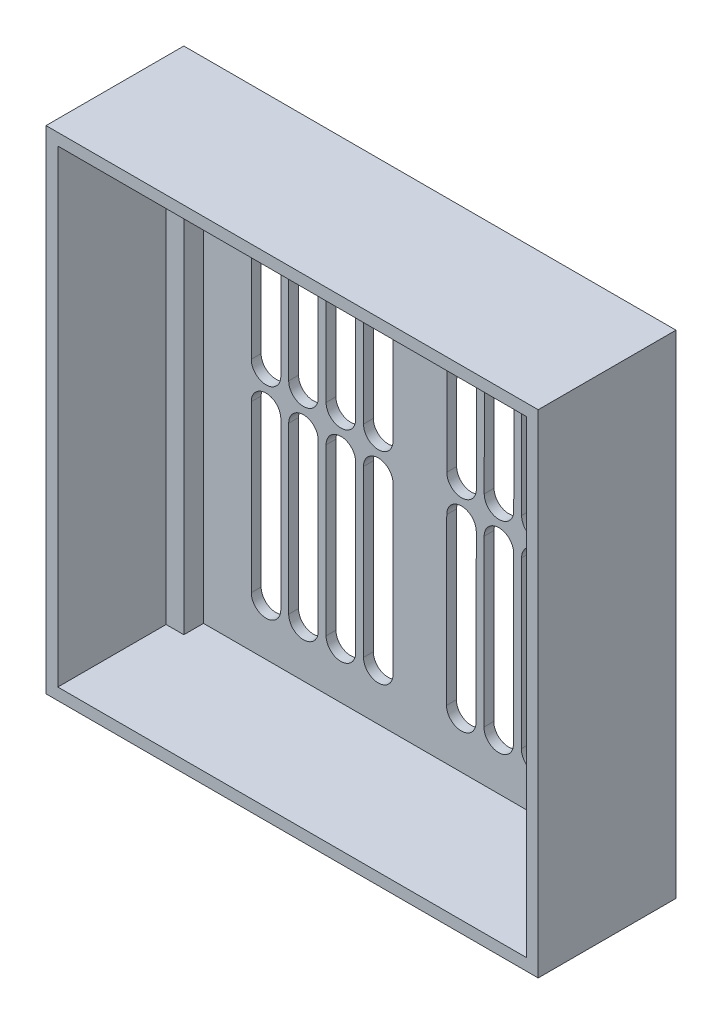
SolidWorks part; units mm, degrees
ref_plane "Plano frontal" through (0, 0, 0) normal (0, 0, 1) x (1, 0, 0)
ref_plane "Plano superior" through (0, 0, 0) normal (0, 1, 0) x (1, 0, 0)
ref_plane "Plano direito" through (0, 0, 0) normal (1, 0, 0) x (0, 0, -1)
sketch "Esboço1" plane through (0, 0, 0) normal (0, 0, 1) x (1, 0, 0)
  line L1 (-16.5696, 239.8339) -> (233.4304, 239.8339)
  line L2 (-16.5696, 239.8339) -> (-16.5696, -10.1661)
  line L3 (-16.5696, -10.1661) -> (233.4304, -10.1661)
  line L4 (233.4304, 239.8339) -> (233.4304, -10.1661)
  dimension "D1" = 250
  dimension "D2" = 250
extrude "Ressalto-extrusão1" add sketch "Esboço1" along normal blind 70 contours L2 L1 L4 L3
sketch "Esboço2" plane through (0, 0, 70) normal (0, 0, 1) x (1, 0, 0)
  line L0 (233.4304, 239.8339) -> (233.4304, -10.1661) construction
  line L1 (-10.5696, 233.8339) -> (227.4304, 233.8339)
  line L2 (-10.5696, 233.8339) -> (-10.5696, -4.1661)
  line L3 (-10.5696, -4.1661) -> (227.4304, -4.1661)
  line L4 (227.4304, 233.8339) -> (227.4304, -4.1661)
  line L5 (-16.5696, 239.8339) -> (233.4304, 239.8339) construction
  line L6 (-16.5696, 239.8339) -> (-16.5696, -10.1661) construction
  line L7 (-16.5696, -10.1661) -> (233.4304, -10.1661) construction
  dimension "D1" = 6
  dimension "D2" = 6
  dimension "D3" = 6
  dimension "D4" = 6
extrude "Corte-extrusão1" cut sketch "Esboço2" against normal blind 55
sketch "Esboço3" plane through (0, 0, 15) normal (0, 0, 1) x (1, 0, 0)
  line L0 (16.5131, 123.2364) -> (114.7807, 123.244)
  line L1 (16.3207, 123.1057) -> (16.3131, 223.614)
  line L2 (16.3748, 223.7141) -> (114.8731, 223.7141)
  line L3 (114.7807, 123.244) -> (114.7731, 223.5216)
  line L4 (215.3156, 223.7537) -> (117.0479, 223.7536)
  line L5 (215.5079, 223.8844) -> (215.5079, 123.3761)
  line L6 (117.0479, 123.4759) -> (215.5079, 123.3761)
  line L7 (117.0479, 223.7536) -> (117.0479, 123.4759)
  line L10 (16.567, 20.9373) -> (114.8346, 20.9449)
  line L11 (16.3746, 20.8067) -> (16.367, 121.3149)
  line L12 (16.4288, 121.4073) -> (99.2081, 121.4137)
  line L13 (114.8346, 20.9449) -> (114.827, 121.2225)
  line L14 (215.3478, 121.4314) -> (117.0801, 121.4238)
  line L15 (215.5401, 121.5621) -> (215.5477, 21.0538)
  line L16 (215.486, 20.9614) -> (116.9877, 20.9538)
  line L17 (117.0801, 121.4238) -> (117.0877, 21.1462)
  line L21 (-16.5696, -10.1661) -> (233.4304, -10.1661) construction
  line L23 (114.7807, 123.244) -> (117.0801, 121.4238) construction
  line L24 (99.2081, 121.4137) -> (114.827, 121.2225)
  line L25 (-16.5696, 239.8339) -> (233.4304, -10.1661) construction
  line L26 (-16.5696, -10.1661) -> (233.4304, 239.8339) construction
  arc A0 (59.4431, 138.154) -> (59.4431, 125.154) centre (59.4431, 131.654) ccw
  arc A1 (59.4431, 125.154) -> (59.4431, 138.154) centre (59.4431, 131.654) ccw
  arc A2 (40.4431, 138.154) -> (40.4431, 125.154) centre (40.4431, 131.654) ccw
  arc A3 (40.4431, 125.154) -> (40.4431, 138.154) centre (40.4431, 131.654) ccw
  arc A4 (40.4431, 152.154) -> (40.4431, 139.154) centre (40.4431, 145.654) ccw
  arc A5 (40.4431, 139.154) -> (40.4431, 152.154) centre (40.4431, 145.654) ccw
  arc A6 (59.4431, 152.154) -> (59.4431, 139.154) centre (59.4431, 145.654) ccw
  arc A7 (59.4431, 139.154) -> (59.4431, 152.154) centre (59.4431, 145.654) ccw
  arc A8 (78.4431, 152.154) -> (78.4431, 139.154) centre (78.4431, 145.654) ccw
  arc A9 (78.4431, 139.154) -> (78.4431, 152.154) centre (78.4431, 145.654) ccw
  arc A10 (78.4431, 138.154) -> (78.4431, 125.154) centre (78.4431, 131.654) ccw
  arc A11 (78.4431, 125.154) -> (78.4431, 138.154) centre (78.4431, 131.654) ccw
  arc A12 (97.4431, 138.154) -> (97.4431, 125.154) centre (97.4431, 131.654) ccw
  arc A13 (97.4431, 125.154) -> (97.4431, 138.154) centre (97.4431, 131.654) ccw
  arc A14 (97.4431, 152.154) -> (97.4431, 139.154) centre (97.4431, 145.654) ccw
  arc A15 (97.4431, 139.154) -> (97.4431, 152.154) centre (97.4431, 145.654) ccw
  arc A16 (97.4431, 166.154) -> (97.4431, 153.154) centre (97.4431, 159.654) ccw
  arc A17 (97.4431, 153.154) -> (97.4431, 166.154) centre (97.4431, 159.654) ccw
  arc A18 (78.4431, 166.154) -> (78.4431, 153.154) centre (78.4431, 159.654) ccw
  arc A19 (78.4431, 153.154) -> (78.4431, 166.154) centre (78.4431, 159.654) ccw
  arc A20 (59.4431, 166.154) -> (59.4431, 153.154) centre (59.4431, 159.654) ccw
  arc A21 (59.4431, 153.154) -> (59.4431, 166.154) centre (59.4431, 159.654) ccw
  arc A22 (40.4431, 166.154) -> (40.4431, 153.154) centre (40.4431, 159.654) ccw
  arc A23 (40.4431, 153.154) -> (40.4431, 166.154) centre (40.4431, 159.654) ccw
  arc A24 (40.4431, 180.154) -> (40.4431, 167.154) centre (40.4431, 173.654) ccw
  arc A25 (40.4431, 167.154) -> (40.4431, 180.154) centre (40.4431, 173.654) ccw
  arc A26 (59.4431, 180.154) -> (59.4431, 167.154) centre (59.4431, 173.654) ccw
  arc A27 (59.4431, 167.154) -> (59.4431, 180.154) centre (59.4431, 173.654) ccw
  arc A28 (78.4431, 180.154) -> (78.4431, 167.154) centre (78.4431, 173.654) ccw
  arc A29 (78.4431, 167.154) -> (78.4431, 180.154) centre (78.4431, 173.654) ccw
  arc A30 (97.4431, 180.154) -> (97.4431, 167.154) centre (97.4431, 173.654) ccw
  arc A31 (97.4431, 167.154) -> (97.4431, 180.154) centre (97.4431, 173.654) ccw
  arc A32 (97.4431, 194.154) -> (97.4431, 181.154) centre (97.4431, 187.654) ccw
  arc A33 (97.4431, 181.154) -> (97.4431, 194.154) centre (97.4431, 187.654) ccw
  arc A34 (78.4431, 194.154) -> (78.4431, 181.154) centre (78.4431, 187.654) ccw
  arc A35 (78.4431, 181.154) -> (78.4431, 194.154) centre (78.4431, 187.654) ccw
  arc A36 (59.4431, 194.154) -> (59.4431, 181.154) centre (59.4431, 187.654) ccw
  arc A37 (59.4431, 181.154) -> (59.4431, 194.154) centre (59.4431, 187.654) ccw
  arc A38 (40.4431, 194.154) -> (40.4431, 181.154) centre (40.4431, 187.654) ccw
  arc A39 (40.4431, 181.154) -> (40.4431, 194.154) centre (40.4431, 187.654) ccw
  arc A40 (40.4431, 208.154) -> (40.4431, 195.154) centre (40.4431, 201.654) ccw
  arc A41 (40.4431, 195.154) -> (40.4431, 208.154) centre (40.4431, 201.654) ccw
  arc A42 (59.4431, 208.154) -> (59.4431, 195.154) centre (59.4431, 201.654) ccw
  arc A43 (59.4431, 195.154) -> (59.4431, 208.154) centre (59.4431, 201.654) ccw
  arc A44 (78.4431, 208.154) -> (78.4431, 195.154) centre (78.4431, 201.654) ccw
  arc A45 (78.4431, 195.154) -> (78.4431, 208.154) centre (78.4431, 201.654) ccw
  arc A46 (97.4431, 208.154) -> (97.4431, 195.154) centre (97.4431, 201.654) ccw
  arc A47 (97.4431, 195.154) -> (97.4431, 208.154) centre (97.4431, 201.654) ccw
  arc A48 (97.4431, 222.154) -> (97.4431, 209.154) centre (97.4431, 215.654) ccw
  arc A49 (97.4431, 209.154) -> (97.4431, 222.154) centre (97.4431, 215.654) ccw
  arc A50 (78.4431, 222.154) -> (78.4431, 209.154) centre (78.4431, 215.654) ccw
  arc A51 (78.4431, 209.154) -> (78.4431, 222.154) centre (78.4431, 215.654) ccw
  arc A52 (59.4431, 222.154) -> (59.4431, 209.154) centre (59.4431, 215.654) ccw
  arc A53 (59.4431, 209.154) -> (59.4431, 222.154) centre (59.4431, 215.654) ccw
  arc A54 (40.4431, 222.154) -> (40.4431, 209.154) centre (40.4431, 215.654) ccw
  arc A55 (40.4431, 209.154) -> (40.4431, 222.154) centre (40.4431, 215.654) ccw
  circle A56 centre (20.8131, 210.774) radius 0.975
  circle A57 centre (20.9431, 217.524) radius 0.975
  circle A58 centre (110.4831, 207.064) radius 0.975
  circle A59 centre (110.4831, 213.114) radius 0.975
  circle A60 centre (110.6631, 136.644) radius 0.975
  circle A61 centre (110.6031, 142.634) radius 0.975
  circle A62 centre (20.6431, 132.314) radius 0.975
  circle A63 centre (20.6431, 138.364) radius 0.975
  arc A64 (172.3779, 208.8361) -> (172.3779, 221.8361) centre (172.3779, 215.3361) ccw
  arc A65 (172.3779, 221.8361) -> (172.3779, 208.8361) centre (172.3779, 215.3361) ccw
  arc A66 (191.3779, 208.8361) -> (191.3779, 221.8361) centre (191.3779, 215.3361) ccw
  arc A67 (191.3779, 221.8361) -> (191.3779, 208.8361) centre (191.3779, 215.3361) ccw
  arc A68 (191.3779, 194.8361) -> (191.3779, 207.8361) centre (191.3779, 201.3361) ccw
  arc A69 (191.3779, 207.8361) -> (191.3779, 194.8361) centre (191.3779, 201.3361) ccw
  arc A70 (172.3779, 194.8361) -> (172.3779, 207.8361) centre (172.3779, 201.3361) ccw
  arc A71 (172.3779, 207.8361) -> (172.3779, 194.8361) centre (172.3779, 201.3361) ccw
  arc A72 (153.3779, 194.8361) -> (153.3779, 207.8361) centre (153.3779, 201.3361) ccw
  arc A73 (153.3779, 207.8361) -> (153.3779, 194.8361) centre (153.3779, 201.3361) ccw
  arc A74 (153.3779, 208.8361) -> (153.3779, 221.8361) centre (153.3779, 215.3361) ccw
  arc A75 (153.3779, 221.8361) -> (153.3779, 208.8361) centre (153.3779, 215.3361) ccw
  arc A76 (134.3779, 208.8361) -> (134.3779, 221.8361) centre (134.3779, 215.3361) ccw
  arc A77 (134.3779, 221.8361) -> (134.3779, 208.8361) centre (134.3779, 215.3361) ccw
  arc A78 (134.3779, 194.8361) -> (134.3779, 207.8361) centre (134.3779, 201.3361) ccw
  arc A79 (134.3779, 207.8361) -> (134.3779, 194.8361) centre (134.3779, 201.3361) ccw
  arc A80 (134.3779, 180.8361) -> (134.3779, 193.8361) centre (134.3779, 187.3361) ccw
  arc A81 (134.3779, 193.8361) -> (134.3779, 180.8361) centre (134.3779, 187.3361) ccw
  arc A82 (153.3779, 180.8361) -> (153.3779, 193.8361) centre (153.3779, 187.3361) ccw
  arc A83 (153.3779, 193.8361) -> (153.3779, 180.8361) centre (153.3779, 187.3361) ccw
  arc A84 (172.3779, 180.8361) -> (172.3779, 193.8361) centre (172.3779, 187.3361) ccw
  arc A85 (172.3779, 193.8361) -> (172.3779, 180.8361) centre (172.3779, 187.3361) ccw
  arc A86 (191.3779, 180.8361) -> (191.3779, 193.8361) centre (191.3779, 187.3361) ccw
  arc A87 (191.3779, 193.8361) -> (191.3779, 180.8361) centre (191.3779, 187.3361) ccw
  arc A88 (191.3779, 166.8361) -> (191.3779, 179.8361) centre (191.3779, 173.3361) ccw
  arc A89 (191.3779, 179.8361) -> (191.3779, 166.8361) centre (191.3779, 173.3361) ccw
  arc A90 (172.3779, 166.8361) -> (172.3779, 179.8361) centre (172.3779, 173.3361) ccw
  arc A91 (172.3779, 179.8361) -> (172.3779, 166.8361) centre (172.3779, 173.3361) ccw
  arc A92 (153.3779, 166.8361) -> (153.3779, 179.8361) centre (153.3779, 173.3361) ccw
  arc A93 (153.3779, 179.8361) -> (153.3779, 166.8361) centre (153.3779, 173.3361) ccw
  arc A94 (134.3779, 166.8361) -> (134.3779, 179.8361) centre (134.3779, 173.3361) ccw
  arc A95 (134.3779, 179.8361) -> (134.3779, 166.8361) centre (134.3779, 173.3361) ccw
  arc A96 (134.3779, 152.8361) -> (134.3779, 165.8361) centre (134.3779, 159.3361) ccw
  arc A97 (134.3779, 165.8361) -> (134.3779, 152.8361) centre (134.3779, 159.3361) ccw
  arc A98 (153.3779, 152.8361) -> (153.3779, 165.8361) centre (153.3779, 159.3361) ccw
  arc A99 (153.3779, 165.8361) -> (153.3779, 152.8361) centre (153.3779, 159.3361) ccw
  arc A100 (172.3779, 152.8361) -> (172.3779, 165.8361) centre (172.3779, 159.3361) ccw
  arc A101 (172.3779, 165.8361) -> (172.3779, 152.8361) centre (172.3779, 159.3361) ccw
  arc A102 (191.3779, 152.8361) -> (191.3779, 165.8361) centre (191.3779, 159.3361) ccw
  arc A103 (191.3779, 165.8361) -> (191.3779, 152.8361) centre (191.3779, 159.3361) ccw
  arc A104 (191.3779, 138.8361) -> (191.3779, 151.8361) centre (191.3779, 145.3361) ccw
  arc A105 (191.3779, 151.8361) -> (191.3779, 138.8361) centre (191.3779, 145.3361) ccw
  arc A106 (172.3779, 138.8361) -> (172.3779, 151.8361) centre (172.3779, 145.3361) ccw
  arc A107 (172.3779, 151.8361) -> (172.3779, 138.8361) centre (172.3779, 145.3361) ccw
  arc A108 (153.3779, 138.8361) -> (153.3779, 151.8361) centre (153.3779, 145.3361) ccw
  arc A109 (153.3779, 151.8361) -> (153.3779, 138.8361) centre (153.3779, 145.3361) ccw
  arc A110 (134.3779, 138.8361) -> (134.3779, 151.8361) centre (134.3779, 145.3361) ccw
  arc A111 (134.3779, 151.8361) -> (134.3779, 138.8361) centre (134.3779, 145.3361) ccw
  arc A112 (134.3779, 124.8361) -> (134.3779, 137.8361) centre (134.3779, 131.3361) ccw
  arc A113 (134.3779, 137.8361) -> (134.3779, 124.8361) centre (134.3779, 131.3361) ccw
  arc A114 (153.3779, 124.8361) -> (153.3779, 137.8361) centre (153.3779, 131.3361) ccw
  arc A115 (153.3779, 137.8361) -> (153.3779, 124.8361) centre (153.3779, 131.3361) ccw
  arc A116 (172.3779, 124.8361) -> (172.3779, 137.8361) centre (172.3779, 131.3361) ccw
  arc A117 (172.3779, 137.8361) -> (172.3779, 124.8361) centre (172.3779, 131.3361) ccw
  arc A118 (191.3779, 124.8361) -> (191.3779, 137.8361) centre (191.3779, 131.3361) ccw
  arc A119 (191.3779, 137.8361) -> (191.3779, 124.8361) centre (191.3779, 131.3361) ccw
  circle A120 centre (211.0079, 136.2161) radius 0.975
  circle A121 centre (210.8779, 129.4661) radius 0.975
  circle A122 centre (121.3379, 139.9261) radius 0.975
  circle A123 centre (121.3379, 133.8761) radius 0.975
  circle A124 centre (121.1579, 210.3461) radius 0.975
  circle A125 centre (121.2179, 204.3561) radius 0.975
  circle A126 centre (211.1779, 214.6761) radius 0.975
  circle A127 centre (211.1779, 208.6261) radius 0.975
  arc A128 (59.497, 35.8549) -> (59.497, 22.8549) centre (59.497, 29.3549) ccw
  arc A129 (59.497, 22.8549) -> (59.497, 35.8549) centre (59.497, 29.3549) ccw
  arc A130 (40.497, 35.8549) -> (40.497, 22.8549) centre (40.497, 29.3549) ccw
  arc A131 (40.497, 22.8549) -> (40.497, 35.8549) centre (40.497, 29.3549) ccw
  arc A132 (40.497, 49.8549) -> (40.497, 36.8549) centre (40.497, 43.3549) ccw
  arc A133 (40.497, 36.8549) -> (40.497, 49.8549) centre (40.497, 43.3549) ccw
  arc A134 (59.497, 49.8549) -> (59.497, 36.8549) centre (59.497, 43.3549) ccw
  arc A135 (59.497, 36.8549) -> (59.497, 49.8549) centre (59.497, 43.3549) ccw
  arc A136 (78.497, 49.8549) -> (78.497, 36.8549) centre (78.497, 43.3549) ccw
  arc A137 (78.497, 36.8549) -> (78.497, 49.8549) centre (78.497, 43.3549) ccw
  arc A138 (78.497, 35.8549) -> (78.497, 22.8549) centre (78.497, 29.3549) ccw
  arc A139 (78.497, 22.8549) -> (78.497, 35.8549) centre (78.497, 29.3549) ccw
  arc A140 (97.497, 35.8549) -> (97.497, 22.8549) centre (97.497, 29.3549) ccw
  arc A141 (97.497, 22.8549) -> (97.497, 35.8549) centre (97.497, 29.3549) ccw
  arc A142 (97.497, 49.8549) -> (97.497, 36.8549) centre (97.497, 43.3549) ccw
  arc A143 (97.497, 36.8549) -> (97.497, 49.8549) centre (97.497, 43.3549) ccw
  arc A144 (97.497, 63.8549) -> (97.497, 50.8549) centre (97.497, 57.3549) ccw
  arc A145 (97.497, 50.8549) -> (97.497, 63.8549) centre (97.497, 57.3549) ccw
  arc A146 (78.497, 63.8549) -> (78.497, 50.8549) centre (78.497, 57.3549) ccw
  arc A147 (78.497, 50.8549) -> (78.497, 63.8549) centre (78.497, 57.3549) ccw
  arc A148 (59.497, 63.8549) -> (59.497, 50.8549) centre (59.497, 57.3549) ccw
  arc A149 (59.497, 50.8549) -> (59.497, 63.8549) centre (59.497, 57.3549) ccw
  arc A150 (40.497, 63.8549) -> (40.497, 50.8549) centre (40.497, 57.3549) ccw
  arc A151 (40.497, 50.8549) -> (40.497, 63.8549) centre (40.497, 57.3549) ccw
  arc A152 (40.497, 77.8549) -> (40.497, 64.8549) centre (40.497, 71.3549) ccw
  arc A153 (40.497, 64.8549) -> (40.497, 77.8549) centre (40.497, 71.3549) ccw
  arc A154 (59.497, 77.8549) -> (59.497, 64.8549) centre (59.497, 71.3549) ccw
  arc A155 (59.497, 64.8549) -> (59.497, 77.8549) centre (59.497, 71.3549) ccw
  arc A156 (78.497, 77.8549) -> (78.497, 64.8549) centre (78.497, 71.3549) ccw
  arc A157 (78.497, 64.8549) -> (78.497, 77.8549) centre (78.497, 71.3549) ccw
  arc A158 (97.497, 77.8549) -> (97.497, 64.8549) centre (97.497, 71.3549) ccw
  arc A159 (97.497, 64.8549) -> (97.497, 77.8549) centre (97.497, 71.3549) ccw
  arc A160 (97.497, 91.8549) -> (97.497, 78.8549) centre (97.497, 85.3549) ccw
  arc A161 (97.497, 78.8549) -> (97.497, 91.8549) centre (97.497, 85.3549) ccw
  arc A162 (78.497, 91.8549) -> (78.497, 78.8549) centre (78.497, 85.3549) ccw
  arc A163 (78.497, 78.8549) -> (78.497, 91.8549) centre (78.497, 85.3549) ccw
  arc A164 (59.497, 91.8549) -> (59.497, 78.8549) centre (59.497, 85.3549) ccw
  arc A165 (59.497, 78.8549) -> (59.497, 91.8549) centre (59.497, 85.3549) ccw
  arc A166 (40.497, 91.8549) -> (40.497, 78.8549) centre (40.497, 85.3549) ccw
  arc A167 (40.497, 78.8549) -> (40.497, 91.8549) centre (40.497, 85.3549) ccw
  arc A168 (40.497, 105.8549) -> (40.497, 92.8549) centre (40.497, 99.3549) ccw
  arc A169 (40.497, 92.8549) -> (40.497, 105.8549) centre (40.497, 99.3549) ccw
  arc A170 (59.497, 105.8549) -> (59.497, 92.8549) centre (59.497, 99.3549) ccw
  arc A171 (59.497, 92.8549) -> (59.497, 105.8549) centre (59.497, 99.3549) ccw
  arc A172 (78.497, 105.8549) -> (78.497, 92.8549) centre (78.497, 99.3549) ccw
  arc A173 (78.497, 92.8549) -> (78.497, 105.8549) centre (78.497, 99.3549) ccw
  arc A174 (97.497, 105.8549) -> (97.497, 92.8549) centre (97.497, 99.3549) ccw
  arc A175 (97.497, 92.8549) -> (97.497, 105.8549) centre (97.497, 99.3549) ccw
  arc A176 (97.497, 119.8549) -> (97.497, 106.8549) centre (97.497, 113.3549) ccw
  arc A177 (97.497, 106.8549) -> (97.497, 119.8549) centre (97.497, 113.3549) ccw
  arc A178 (78.497, 119.8549) -> (78.497, 106.8549) centre (78.497, 113.3549) ccw
  arc A179 (78.497, 106.8549) -> (78.497, 119.8549) centre (78.497, 113.3549) ccw
  arc A180 (59.497, 119.8549) -> (59.497, 106.8549) centre (59.497, 113.3549) ccw
  arc A181 (59.497, 106.8549) -> (59.497, 119.8549) centre (59.497, 113.3549) ccw
  arc A182 (40.497, 119.8549) -> (40.497, 106.8549) centre (40.497, 113.3549) ccw
  arc A183 (40.497, 106.8549) -> (40.497, 119.8549) centre (40.497, 113.3549) ccw
  circle A184 centre (20.867, 108.4749) radius 0.975
  circle A185 centre (20.997, 115.2249) radius 0.975
  circle A186 centre (110.537, 104.7649) radius 0.975
  circle A187 centre (110.537, 110.8149) radius 0.975
  circle A188 centre (110.717, 34.3449) radius 0.975
  circle A189 centre (110.657, 40.3349) radius 0.975
  circle A190 centre (20.697, 30.0149) radius 0.975
  circle A191 centre (20.697, 36.0649) radius 0.975
  arc A192 (172.4177, 106.5138) -> (172.4177, 119.5138) centre (172.4177, 113.0138) ccw
  arc A193 (172.4177, 119.5138) -> (172.4177, 106.5138) centre (172.4177, 113.0138) ccw
  arc A194 (191.4177, 106.5138) -> (191.4177, 119.5138) centre (191.4177, 113.0138) ccw
  arc A195 (191.4177, 119.5138) -> (191.4177, 106.5138) centre (191.4177, 113.0138) ccw
  arc A196 (191.4177, 92.5138) -> (191.4177, 105.5138) centre (191.4177, 99.0138) ccw
  arc A197 (191.4177, 105.5138) -> (191.4177, 92.5138) centre (191.4177, 99.0138) ccw
  arc A198 (172.4177, 92.5138) -> (172.4177, 105.5138) centre (172.4177, 99.0138) ccw
  arc A199 (172.4177, 105.5138) -> (172.4177, 92.5138) centre (172.4177, 99.0138) ccw
  arc A200 (153.4177, 92.5138) -> (153.4177, 105.5138) centre (153.4177, 99.0138) ccw
  arc A201 (153.4177, 105.5138) -> (153.4177, 92.5138) centre (153.4177, 99.0138) ccw
  arc A202 (153.4177, 106.5138) -> (153.4177, 119.5138) centre (153.4177, 113.0138) ccw
  arc A203 (153.4177, 119.5138) -> (153.4177, 106.5138) centre (153.4177, 113.0138) ccw
  arc A204 (134.4177, 106.5138) -> (134.4177, 119.5138) centre (134.4177, 113.0138) ccw
  arc A205 (134.4177, 119.5138) -> (134.4177, 106.5138) centre (134.4177, 113.0138) ccw
  arc A206 (134.4177, 92.5138) -> (134.4177, 105.5138) centre (134.4177, 99.0138) ccw
  arc A207 (134.4177, 105.5138) -> (134.4177, 92.5138) centre (134.4177, 99.0138) ccw
  arc A208 (134.4177, 78.5138) -> (134.4177, 91.5138) centre (134.4177, 85.0138) ccw
  arc A209 (134.4177, 91.5138) -> (134.4177, 78.5138) centre (134.4177, 85.0138) ccw
  arc A210 (153.4177, 78.5138) -> (153.4177, 91.5138) centre (153.4177, 85.0138) ccw
  arc A211 (153.4177, 91.5138) -> (153.4177, 78.5138) centre (153.4177, 85.0138) ccw
  arc A212 (172.4177, 78.5138) -> (172.4177, 91.5138) centre (172.4177, 85.0138) ccw
  arc A213 (172.4177, 91.5138) -> (172.4177, 78.5138) centre (172.4177, 85.0138) ccw
  arc A214 (191.4177, 78.5138) -> (191.4177, 91.5138) centre (191.4177, 85.0138) ccw
  arc A215 (191.4177, 91.5138) -> (191.4177, 78.5138) centre (191.4177, 85.0138) ccw
  arc A216 (191.4177, 64.5138) -> (191.4177, 77.5138) centre (191.4177, 71.0138) ccw
  arc A217 (191.4177, 77.5138) -> (191.4177, 64.5138) centre (191.4177, 71.0138) ccw
  arc A218 (172.4177, 64.5138) -> (172.4177, 77.5138) centre (172.4177, 71.0138) ccw
  arc A219 (172.4177, 77.5138) -> (172.4177, 64.5138) centre (172.4177, 71.0138) ccw
  arc A220 (153.4177, 64.5138) -> (153.4177, 77.5138) centre (153.4177, 71.0138) ccw
  arc A221 (153.4177, 77.5138) -> (153.4177, 64.5138) centre (153.4177, 71.0138) ccw
  arc A222 (134.4177, 64.5138) -> (134.4177, 77.5138) centre (134.4177, 71.0138) ccw
  arc A223 (134.4177, 77.5138) -> (134.4177, 64.5138) centre (134.4177, 71.0138) ccw
  arc A224 (134.4177, 50.5138) -> (134.4177, 63.5138) centre (134.4177, 57.0138) ccw
  arc A225 (134.4177, 63.5138) -> (134.4177, 50.5138) centre (134.4177, 57.0138) ccw
  arc A226 (153.4177, 50.5138) -> (153.4177, 63.5138) centre (153.4177, 57.0138) ccw
  arc A227 (153.4177, 63.5138) -> (153.4177, 50.5138) centre (153.4177, 57.0138) ccw
  arc A228 (172.4177, 50.5138) -> (172.4177, 63.5138) centre (172.4177, 57.0138) ccw
  arc A229 (172.4177, 63.5138) -> (172.4177, 50.5138) centre (172.4177, 57.0138) ccw
  arc A230 (191.4177, 50.5138) -> (191.4177, 63.5138) centre (191.4177, 57.0138) ccw
  arc A231 (191.4177, 63.5138) -> (191.4177, 50.5138) centre (191.4177, 57.0138) ccw
  arc A232 (191.4177, 36.5138) -> (191.4177, 49.5138) centre (191.4177, 43.0138) ccw
  arc A233 (191.4177, 49.5138) -> (191.4177, 36.5138) centre (191.4177, 43.0138) ccw
  arc A234 (172.4177, 36.5138) -> (172.4177, 49.5138) centre (172.4177, 43.0138) ccw
  arc A235 (172.4177, 49.5138) -> (172.4177, 36.5138) centre (172.4177, 43.0138) ccw
  arc A236 (153.4177, 36.5138) -> (153.4177, 49.5138) centre (153.4177, 43.0138) ccw
  arc A237 (153.4177, 49.5138) -> (153.4177, 36.5138) centre (153.4177, 43.0138) ccw
  arc A238 (134.4177, 36.5138) -> (134.4177, 49.5138) centre (134.4177, 43.0138) ccw
  arc A239 (134.4177, 49.5138) -> (134.4177, 36.5138) centre (134.4177, 43.0138) ccw
  arc A240 (134.4177, 22.5138) -> (134.4177, 35.5138) centre (134.4177, 29.0138) ccw
  arc A241 (134.4177, 35.5138) -> (134.4177, 22.5138) centre (134.4177, 29.0138) ccw
  arc A242 (153.4177, 22.5138) -> (153.4177, 35.5138) centre (153.4177, 29.0138) ccw
  arc A243 (153.4177, 35.5138) -> (153.4177, 22.5138) centre (153.4177, 29.0138) ccw
  arc A244 (172.4177, 22.5138) -> (172.4177, 35.5138) centre (172.4177, 29.0138) ccw
  arc A245 (172.4177, 35.5138) -> (172.4177, 22.5138) centre (172.4177, 29.0138) ccw
  arc A246 (191.4177, 22.5138) -> (191.4177, 35.5138) centre (191.4177, 29.0138) ccw
  arc A247 (191.4177, 35.5138) -> (191.4177, 22.5138) centre (191.4177, 29.0138) ccw
  circle A248 centre (211.0477, 33.8938) radius 0.975
  circle A249 centre (210.9177, 27.1438) radius 0.975
  circle A250 centre (121.3777, 37.6038) radius 0.975
  circle A251 centre (121.3777, 31.5538) radius 0.975
  circle A252 centre (121.1977, 108.0238) radius 0.975
  circle A253 centre (121.2577, 102.0338) radius 0.975
  circle A254 centre (211.2177, 112.3538) radius 0.975
  circle A255 centre (211.2177, 106.3038) radius 0.975
  point P135 (166.2214, 173.6225)
  point P406 (166.2574, 71.2965)
  point P544 (115.9304, 122.3339)
  point P546 (115.9304, 122.3339)
sketch "Esboço5" plane through (0, 239.8339, 0) normal (0, 1, 0) x (1, 0, 0)
  line L0 (39.532, 0) -> (39.532, -40.1721)
  line L1 (-16.5696, 0) -> (233.4304, 0) construction
  line L2 (-48.9022, 48.2621) -> (39.532, -40.1721)
  line L3 (127.9662, 48.2621) -> (39.532, -40.1721)
  line L4 (-48.9022, 48.2621) -> (-150.6401, 150) construction
  line L5 (39.532, 0) -> (39.532, 150) construction
  line L6 (-150.6401, 150) -> (229.7041, 150) construction
  line L7 (127.9662, 48.2621) -> (375.3202, 295.6161) construction
  arc A0 (-48.9022, 48.2621) -> (127.9662, 48.2621) centre (39.532, -40.1721) cw
  dimension "D1" = 90
  dimension "D2" = 45
sketch "Esboço6" plane through (0, 0, 15) normal (0, 0, 1) x (1, 0, 0)
  line L0 (22.6955, 208.1676) -> (22.6955, 124.154)
  line L1 (37.6955, 208.1676) -> (37.6955, 124.154)
  line L2 (41.6955, 208.1676) -> (41.6955, 124.154)
  line L3 (56.6955, 124.154) -> (56.6955, 208.1676)
  line L4 (60.6955, 208.1676) -> (60.6955, 124.154)
  line L5 (79.6955, 208.1676) -> (79.6955, 124.154)
  line L6 (75.6955, 124.154) -> (75.6955, 208.1676)
  line L7 (94.6955, 124.154) -> (94.6955, 208.1676)
  line L9 (94.6955, 105.5138) -> (94.6955, 21.5002)
  line L17 (-10.5696, 114.8339) -> (227.4304, 114.8339) construction
  line L18 (-10.5696, 233.8339) -> (-10.5696, -4.1661) construction
  line L19 (227.4304, -4.1661) -> (227.4304, 233.8339) construction
  line L20 (75.6955, 105.5138) -> (75.6955, 21.5002)
  line L21 (79.6955, 21.5002) -> (79.6955, 105.5138)
  line L22 (60.6955, 21.5002) -> (60.6955, 105.5138)
  line L23 (56.6955, 105.5138) -> (56.6955, 21.5002)
  line L24 (41.6955, 21.5002) -> (41.6955, 105.5138)
  line L25 (37.6955, 21.5002) -> (37.6955, 105.5138)
  line L26 (22.6955, 21.5002) -> (22.6955, 105.5138)
  line L27 (193.8751, 21.3832) -> (193.9899, 105.3967)
  line L28 (108.418, 215.6572) -> (108.4304, 233.8339) construction
  line L29 (227.4304, 233.8339) -> (-10.5696, 233.8339) construction
  line L30 (178.8751, 21.4037) -> (178.9899, 105.4172)
  line L31 (174.8751, 21.4092) -> (174.9899, 105.4227)
  line L32 (159.9899, 105.4432) -> (159.8751, 21.4297)
  line L33 (155.8751, 21.4351) -> (155.9899, 105.4487)
  line L34 (136.8752, 21.4611) -> (136.99, 105.4746)
  line L35 (140.99, 105.4692) -> (140.8752, 21.4556)
  line L36 (121.99, 105.4951) -> (121.8752, 21.4816)
  line L37 (122.0155, 124.1353) -> (122.1303, 208.1489)
  line L38 (141.0154, 124.1094) -> (141.1302, 208.1229)
  line L39 (137.1302, 208.1284) -> (137.0154, 124.1148)
  line L40 (156.1302, 208.1024) -> (156.0154, 124.0889)
  line L41 (160.0154, 124.0834) -> (160.1302, 208.0969)
  line L42 (175.1302, 208.0764) -> (175.0154, 124.0629)
  line L43 (179.1302, 208.071) -> (179.0154, 124.0574)
  line L44 (194.1302, 208.0505) -> (194.0154, 124.0369)
  line L45 (-10.5696, -4.1661) -> (227.4304, -4.1661) construction
  arc A112 (37.6955, 208.1676) -> (22.6955, 208.1676) centre (30.1955, 208.1676) ccw
  arc A113 (22.6955, 124.154) -> (37.6955, 124.154) centre (30.1955, 124.154) ccw
  arc A114 (41.6955, 208.1676) -> (56.6955, 208.1676) centre (49.1955, 208.1676) cw
  arc A115 (41.6955, 124.154) -> (56.6955, 124.154) centre (49.1955, 124.154) ccw
  arc A116 (60.6955, 208.1676) -> (75.6955, 208.1676) centre (68.1955, 208.1676) cw
  arc A117 (60.6955, 124.154) -> (75.6955, 124.154) centre (68.1955, 124.154) ccw
  arc A118 (79.6955, 208.1676) -> (94.6955, 208.1676) centre (87.1955, 208.1676) cw
  arc A119 (79.6955, 124.154) -> (94.6955, 124.154) centre (87.1955, 124.154) ccw
  arc A128 (79.6955, 105.5138) -> (94.6955, 105.5138) centre (87.1955, 105.5138) cw
  arc A129 (79.6955, 21.5002) -> (94.6955, 21.5002) centre (87.1955, 21.5002) ccw
  arc A130 (60.6955, 105.5138) -> (75.6955, 105.5138) centre (68.1955, 105.5138) cw
  arc A131 (60.6955, 21.5002) -> (75.6955, 21.5002) centre (68.1955, 21.5002) ccw
  arc A132 (41.6955, 105.5138) -> (56.6955, 105.5138) centre (49.1955, 105.5138) cw
  arc A133 (41.6955, 21.5002) -> (56.6955, 21.5002) centre (49.1955, 21.5002) ccw
  arc A134 (22.6955, 105.5138) -> (37.6955, 105.5138) centre (30.1955, 105.5138) cw
  arc A135 (37.6955, 21.5002) -> (22.6955, 21.5002) centre (30.1955, 21.5002) cw
  arc A136 (178.8751, 21.4037) -> (193.8751, 21.3832) centre (186.3751, 21.3935) ccw
  arc A137 (193.9899, 105.3967) -> (178.9899, 105.4172) centre (186.4899, 105.407) ccw
  arc A138 (174.8751, 21.4092) -> (159.8751, 21.4297) centre (167.3751, 21.4194) cw
  arc A139 (174.9899, 105.4227) -> (159.9899, 105.4432) centre (167.4899, 105.433) ccw
  arc A140 (155.8751, 21.4351) -> (140.8752, 21.4556) centre (148.3751, 21.4454) cw
  arc A141 (155.9899, 105.4487) -> (140.99, 105.4692) centre (148.49, 105.4589) ccw
  arc A142 (136.8752, 21.4611) -> (121.8752, 21.4816) centre (129.3752, 21.4713) cw
  arc A143 (136.99, 105.4746) -> (121.99, 105.4951) centre (129.49, 105.4849) ccw
  arc A144 (137.0154, 124.1148) -> (122.0155, 124.1353) centre (129.5154, 124.1251) cw
  arc A145 (137.1302, 208.1284) -> (122.1303, 208.1489) centre (129.6303, 208.1386) ccw
  arc A146 (156.0154, 124.0889) -> (141.0154, 124.1094) centre (148.5154, 124.0991) cw
  arc A147 (156.1302, 208.1024) -> (141.1302, 208.1229) centre (148.6302, 208.1127) ccw
  arc A148 (175.0154, 124.0629) -> (160.0154, 124.0834) centre (167.5154, 124.0731) cw
  arc A149 (175.1302, 208.0764) -> (160.1302, 208.0969) centre (167.6302, 208.0867) ccw
  arc A150 (194.0154, 124.0369) -> (179.0154, 124.0574) centre (186.5154, 124.0472) cw
  arc A151 (179.1302, 208.071) -> (194.1302, 208.0505) centre (186.6302, 208.0607) cw
  point P8 (133.7727, 129.995)
  point P11 (154.9887, 112.193)
  dimension "D1" = 19
  dimension "D2" = 19
  dimension "D3" = 19
  dimension "D4" = 19
  dimension "D14" = 7.5
  dimension "D15" = 7.5
  dimension "D16" = 7.5
  dimension "D17" = 7.5
  dimension "D5" = 19
  dimension "D6" = 19
  dimension "D7" = 19
  dimension "D8" = 19
  dimension "D9" = 18.9745
  dimension "D10" = 19
  dimension "D11" = 19
  dimension "D12" = 19
  dimension "D13" = 21.2174
extrude "Corte-extrusão2" cut sketch "Esboço6" against normal through all
sketch "Esboço7" plane through (0, 0, 15) normal (0, 0, 1) x (1, 0, 0)
  line L0 (-16.5696, 239.8339) -> (233.4304, -10.1661) construction
  line L1 (-1.5696, 224.8339) -> (218.4304, 224.8339)
  line L2 (-1.5696, 224.8339) -> (-1.5696, -4.1661)
  line L3 (-1.5696, -4.1661) -> (218.4304, -4.1661)
  line L4 (218.4304, 224.8339) -> (218.4304, -4.1661)
  line L5 (-16.5696, 239.8339) -> (-16.5696, -10.1661) construction
  line L8 (233.4304, 239.8339) -> (233.4304, -10.1661) construction
  line L9 (-10.5696, -4.1661) -> (227.4304, -4.1661) construction
  dimension "D1" = 15
  dimension "D2" = 0
  dimension "D3" = 15
extrude "Corte-extrusão3" cut sketch "Esboço7" against normal blind 10
